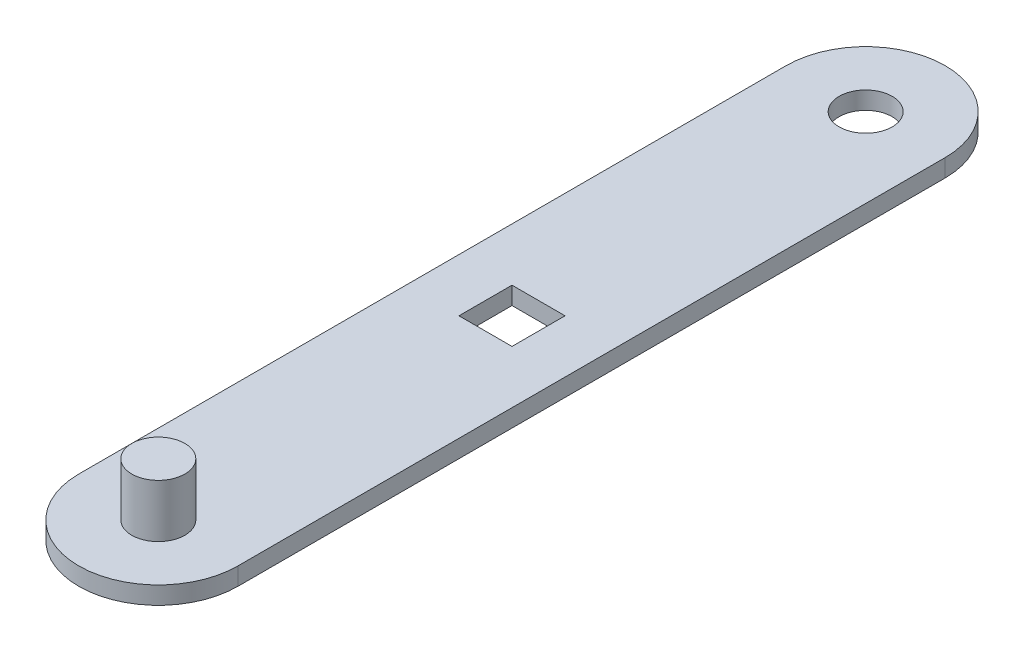
SolidWorks part; units mm, degrees
ref_plane "Front Plane" through (0, 0, 0) normal (0, 0, 1) x (1, 0, 0)
ref_plane "Top Plane" through (0, 0, 0) normal (0, 1, 0) x (1, 0, 0)
ref_plane "Right Plane" through (0, 0, 0) normal (1, 0, 0) x (0, 0, -1)
sketch "Sketch1" plane through (0, 0, 0) normal (0, 1, 0) x (1, 0, 0)
  line L1 (-225, -1000) -> (225, -1000)
  line L2 (-225, -1000) -> (-225, 1000)
  line L3 (-225, 1000) -> (225, 1000)
  line L4 (225, -1000) -> (225, 1000)
  line L5 (-225, -1000) -> (225, 1000) construction
  line L6 (-225, 1000) -> (225, -1000) construction
  arc A0 (225, -1000) -> (-225, -1000) centre (0, -1000) cw
  arc A1 (225, 1000) -> (-225, 1000) centre (0, 1000) ccw
  point P0 (0, 0)
  dimension "D1" = 2000
  dimension "D2" = 450
extrude "Boss-Extrude1" add sketch "Sketch1" along normal blind 50 contours L1 L4 L3 L2 | L3 A1 | A0 L1 region at (0, 0, 0) region at (0, 0, 1095.493) region at (0, 0, -1095.493)
sketch "Sketch2" plane through (0, 50, 0) normal (0, 1, 0) x (1, 0, 0)
  line L0 (-225, -1000) -> (225, -1000)
  line L1 (-225, -1000) -> (-225, 1000) construction
  circle A0 centre (0, -1000) radius 75
extrude "Boss-Extrude2" add sketch "Sketch2" along normal blind 150 contours L0 A0 | L0 A0 region at (0, 50, 968.169) region at (0, 50, 1031.831)
sketch "Sketch3" plane through (0, 50, 0) normal (0, 1, 0) x (1, 0, 0)
  line L0 (-225, 1000) -> (225, 1000)
  circle A0 centre (0, 1000) radius 75
extrude "Cut-Extrude2" cut sketch "Sketch3" against normal blind 250 contours L0 A0 | L0 A0 region at (0, 50, -1031.831) region at (0, 50, -968.169)
sketch "Sketch5" plane through (0, 50, 0) normal (0, 1, 0) x (1, 0, 0)
  line L1 (-75, -75) -> (75, -75)
  line L2 (-75, -75) -> (-75, 75)
  line L3 (-75, 75) -> (75, 75)
  line L4 (75, -75) -> (75, 75)
  line L5 (-75, -75) -> (75, 75) construction
  line L6 (-75, 75) -> (75, -75) construction
  point P0 (0, 0)
  dimension "D1" = 150
  dimension "D2" = 150
extrude "Cut-Extrude3" cut sketch "Sketch5" against normal through all
